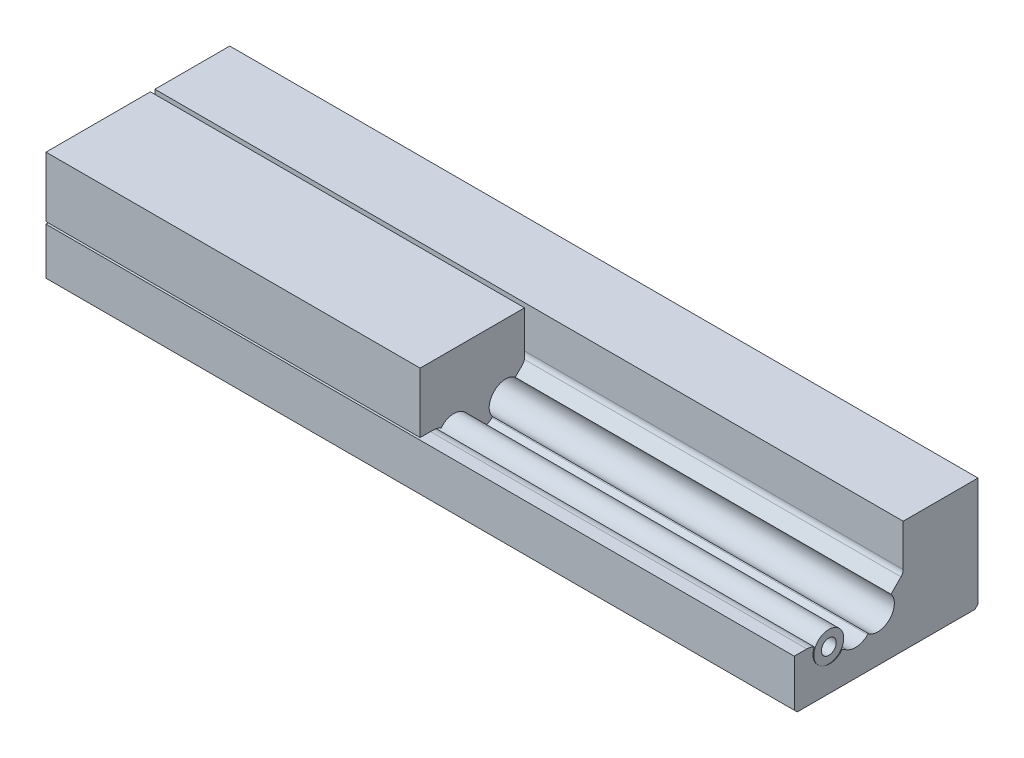
SolidWorks part; units mm, degrees
note: The reader was unsure of these and kept them because the rebuilt part matched: shared geometry of "Sketch1<3>", "Sketch1<4>".
ref_plane "Front Plane" through (0, 0, 0) normal (1, 0, 0) x (0, 1, 0)
ref_plane "Top Plane" through (0, 0, 0) normal (0, 0, 1) x (0, 1, 0)
ref_plane "Right Plane" through (0, 0, 0) normal (0, 1, 0) x (-1, 0, 0)
sketch "Sketch1" plane through (0, 0, 0) normal (1, 0, 0) x (0, 1, 0)
  line L0 (0, 0) -> (-15, 0)
  line L1 (-15, 0) -> (-15, 24.5559)
  line L2 (-15, 24.5559) -> (-7.0603, 24.5559)
  line L3 (-7.0603, 24.5559) -> (-8.6086, 21.8741) construction
  line L4 (0, 0) -> (0, 10)
  line L5 (0, 10) -> (-5.5858, 10)
  line L6 (-6.2929, 10.2929) -> (-7.6304, 11.6304)
  line L7 (-12, 16) -> (-10.7525, 18.1607)
  line L8 (-12, 16) -> (-10.6624, 14.6624)
  line L9 (0, 24.5559) -> (0, 10.6)
  line L10 (0, 10.6) -> (-5.7615, 10.6)
  line L11 (-6.4686, 10.8929) -> (-7.4183, 11.8426)
  line L12 (-10.4503, 14.8746) -> (-10.5399, 14.9642)
  line L13 (-10.8578, 17.3784) -> (-10.4927, 18.0107)
  line L14 (-9.4231, 22.0559) -> (-15, 22.0559) construction
  line L15 (-9.6782, 17.8289) -> (-10.5977, 17.8289) construction
  line L16 (-10.9046, 15.3289) -> (-9.1903, 15.3289) construction
  line L17 (-8.3488, 21.7241) -> (-6.7139, 24.5559) construction
  line L18 (-8.3407, 22.8741) -> (-8.3407, 24.5559)
  line L19 (-8.0407, 22.8741) -> (-8.0407, 24.5559)
  line L20 (-7.0603, 24.5559) -> (0, 24.5559)
  line L21 (-15, 0.4) -> (-14.6, 0)
  line L22 (-14.6, 24.5559) -> (-15, 24.1559)
  arc A0 (-10.8578, 17.3784) -> (-10.5399, 14.9642) centre (-9.1257, 16.3784) ccw
  arc A1 (-11.1176, 17.5284) -> (-10.7521, 14.7521) centre (-9.1257, 16.3784) ccw
  arc A2 (-8.6086, 21.8741) -> (-8.3407, 22.8741) centre (-10.3407, 22.8741) ccw
  arc A3 (-8.3488, 21.7241) -> (-8.0407, 22.8741) centre (-10.3407, 22.8741) ccw
  arc A4 (-5.5858, 10) -> (-6.2929, 10.2929) centre (-5.5858, 11) cw
  arc A5 (-5.7615, 10.6) -> (-6.4686, 10.8929) centre (-5.7615, 11.6) cw
  circle A6 centre (-9.5507, 19.9424) radius 2
  circle A7 centre (-9.5507, 19.9424) radius 1
  ellipse E0 centre (-9.5507, 19.9424) end of major axis (-8.4757, 21.8043) minor radius 2
  ellipse E1 centre (-9.0404, 13.2525) end of major axis (-10.5607, 14.7728) minor radius 2
  point P52 (-6, 10)
  dimension "D21" = 2
  dimension "D22" = 2
  dimension "D24" = 1
  dimension "D27" = 2
  dimension "D1" = 15
  dimension "D2" = 4
  dimension "D3" = 4.3
  dimension "D4" = 0.15
  dimension "D5" = 6
  dimension "D6" = 10
  dimension "D8" = 135
  dimension "D9" = 4
  dimension "D10" = 4.3
  dimension "D11" = 0.15
  dimension "D12" = 0.15
  dimension "D13" = 0.15
  dimension "D7" = 3
  dimension "D14" = 0.6
  dimension "D15" = 0.3
  dimension "D16" = 0.3
  dimension "D17" = 0.3
  dimension "D18" = 30
  dimension "D19" = 2.5
  dimension "D20" = 2.5
  dimension "D23" = 0.3
  dimension "D25" = 0.4
  dimension "D26" = 45
extrude "Boss-Extrude1" add sketch "Sketch1" along normal blind 100 contours E1 L8 L7 E0 A2 L18 L2 L22 L1 L21 L0 L4 L5 A4 L6 | A1 L7 L8
extrude "Boss-Extrude2" add sketch "Sketch1<3>" along normal blind 50 separate body contours E1 L11 A5 L10 L9 L20 L2 L19 A3 E0 L13 A0 L12
sketch "Sketch1<3>" plane through (0, 0, 0) normal (1, 0, 0) x (0, 1, 0) same geometry as "Sketch1"
extrude "Boss-Extrude3" add sketch "Sketch1<4>" along normal up to surface (100 mm away) separate body contours A6 A7 up to face at (100, -9.4143, 14.0568)
sketch "Sketch1<4>" plane through (0, 0, 0) normal (1, 0, 0) x (0, 1, 0) same geometry as "Sketch1"
other "Save Bodies1"
equation "\"tol\" = 0.15mm"
equation "\"D3@Sketch1\"=\"tol\"*2 + \"D2@Sketch1\""
equation "\"D4@Sketch1\"=\"tol\""
equation "\"D9@Sketch1\"=\"D2@Sketch1\""
equation "\"D10@Sketch1\"=\"D3@Sketch1\""
equation "\"D11@Sketch1\"=\"tol\""
equation "\"D12@Sketch1\"=\"tol\""
equation "\"D13@Sketch1\"=\"tol\""
equation "\"D14@Sketch1\"=\"tol\"*4"
equation "\"D15@Sketch1\"=\"tol\"*2"
equation "\"D16@Sketch1\"=\"tol\"*2"
equation "\"D17@Sketch1\"=\"tol\"*2"
equation "\"D23@Sketch1\"=\"tol\"*2"
